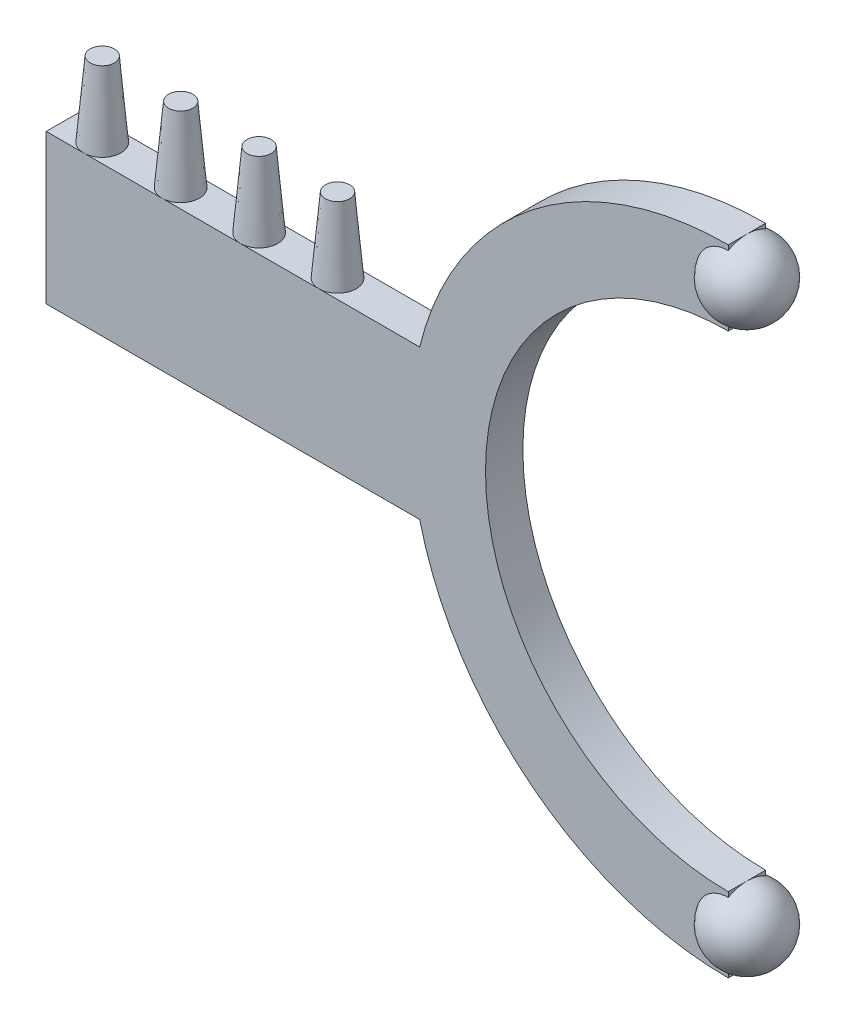
SolidWorks part; units mm, degrees
ref_plane "Front Plane" through (0, 0, 0) normal (0, 0, 1) x (1, 0, 0)
ref_plane "Top Plane" through (0, 0, 0) normal (0, 1, 0) x (1, 0, 0)
ref_plane "Right Plane" through (0, 0, 0) normal (1, 0, 0) x (0, 0, -1)
sketch "Sketch1" plane through (0, 0, 0) normal (0, 0, 1) x (1, 0, 0)
  line L0 (-18.2614, 2) -> (-18.2614, -2)
  line L1 (-8.2614, 2) -> (-18.2614, 2)
  line L2 (-8.2614, -2) -> (-18.2614, -2)
  line L4 (0, -6.5) -> (0, -8.5)
  line L5 (0, 8.5) -> (0, 6.5)
  line L6 (0, 0) -> (0, 2.8656) construction
  arc A0 (0, 6.5) -> (0, -6.5) centre (0, 0) ccw
  arc A1 (0, 8.5) -> (0, -8.5) centre (0, 0) ccw
  arc A4 (0, 8.5) -> (0, 6.5) centre (0, 7.5) ccw
  arc A5 (0, -6.5) -> (0, -8.5) centre (0, -7.5) ccw
  point P5 (-6.5, 0)
  point P11 (-18.2614, 0)
  point P12 (-8.5, 0)
  dimension "D1" = 6.5
  dimension "D2" = 8.5
  dimension "D3" = 2
  dimension "D5" = 4
  dimension "D6" = 10
extrude "Boss-Extrude1" add sketch "Sketch1" along normal mid plane 1 contours A1 L1 L0 L2 | L5 A1 L4 A0 | L5 A4 | L4 A5 region at (-13.3409, 0, 0) region at (-5.1384, 6.5308, 0) region at (-0.4244, 7.5, 0) region at (-0.4244, -7.5, 0)
revolve "Revolve14" add sketch "Sketch1<7>" angle 360 about L6 region at (-0.4244, 7.5, 0) region at (-0.4244, -7.5, 0)
sketch "Sketch1<7>" plane through (0, 0, 0) normal (0, 0, 1) x (1, 0, 0) same geometry as "Sketch1"
sketch "Sketch2" plane through (0, 2, 0) normal (0, 1, 0) x (1, 0, 0)
  line L0 (-18.2614, -0.5) -> (-18.2614, 0.5) construction
  line L1 (-8.2614, -0.5) -> (-8.2614, 0.5) construction
  circle A0 centre (-17.2614, 0) radius 0.5
  circle A1 centre (-15.1614, 0) radius 0.5
  circle A2 centre (-13.0614, 0) radius 0.5
  circle A3 centre (-10.9614, 0) radius 0.5
  point P4 (-18.2614, 0)
  point P6 (-17.2614, 0)
  point P12 (-17.2614, 0)
  dimension "D1" = 1
  dimension "D2" = 1
  dimension "D3" = 4
  dimension "D4" = 9
extrude "Boss-Extrude2" add sketch "Sketch2" along normal blind 2 draft 5
